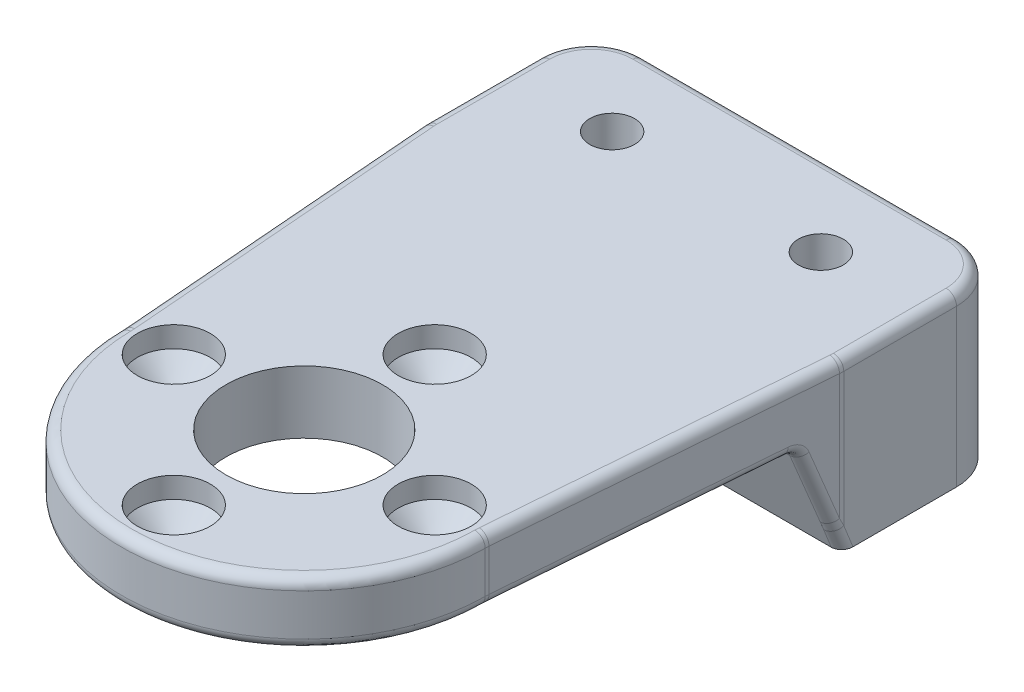
SolidWorks part; units mm, degrees
ref_plane "Front Plane" through (0, 0, 0) normal (0, 0, 1) x (1, 0, 0)
ref_plane "Top Plane" through (0, 0, 0) normal (0, 1, 0) x (1, 0, 0)
ref_plane "Right Plane" through (0, 0, 0) normal (1, 0, 0) x (0, 0, -1)
sketch "Sketch1" plane through (0, 0, 0) normal (0, 1, 0) x (1, 0, 0)
  circle A1 centre (-12.5, 0) radius 1.6
  circle A3 centre (0, 12.5) radius 1.6
  circle A5 centre (12.5, 0) radius 1.6
  circle A7 centre (0, -12.5) radius 1.6
  circle A10 centre (0, 0) radius 17.5
  circle A11 centre (0, 0) radius 7.5
  point P0 (0, 0)
  point P6 (0, 0)
  point P30 (0, 0)
  dimension "D4" = 3.2
  dimension "D1" = 15
  dimension "D2" = 35
  dimension "D5" = 12.5
  dimension "D7" = 4
extrude "Boss-Extrude1" add sketch "Sketch1" along normal blind 4
sketch "Sketch2" plane through (0, 4, 0) normal (0, 1, 0) x (1, 0, 0)
  circle A0 centre (0, -12.5) radius 1.6 construction
  circle A1 centre (0, 0) radius 17.5
  circle A2 centre (0, 0) radius 17.5
  circle A6 centre (0, -12.5) radius 3.5
  circle A7 centre (12.5, 0) radius 3.5
  circle A8 centre (0, 12.5) radius 3.5
  circle A9 centre (-12.5, 0) radius 3.5
  circle A10 centre (0, 0) radius 7.5 construction
  circle A11 centre (0, 0) radius 7.5
  dimension "D2" = 1.9
  dimension "D1" = 0
extrude "Boss-Extrude2" add sketch "Sketch2" along normal blind 2
sketch "Sketch3" plane through (0, 6, 0) normal (0, 1, 0) x (1, 0, 0)
  line L1 (-17.5, 0) -> (-20, 31.5)
  line L2 (17.5, 0) -> (20, 31.5)
  line L5 (-20, 31.5) -> (-20, 47.5)
  line L6 (-20, 47.5) -> (20, 47.5)
  line L7 (20, 31.5) -> (20, 47.5)
  circle A0 centre (0, 0) radius 17.5 construction
  circle A1 centre (0, 0) radius 17.5
  point P4 (0, 47.5)
  circle M6 centre (0, 0) radius 17.5
  dimension "D2" = 31.5
  dimension "D1" = 40
  dimension "D3" = 16
extrude "Boss-Extrude3" add sketch "Sketch3" against normal up to surface (6 mm away) contours L2 L7 L6 L5 L1 M6 region at (0, 6, -30.3876) up to face at (0, 0, 7.5)
sketch "Sketch4" plane through (0, 0, 0) normal (0, -1, 0) x (1, 0, 0)
  line L1 (-20, -47.5) -> (20, -47.5)
  line L2 (-20, -47.5) -> (-20, -31.5)
  line L3 (-20, -31.5) -> (20, -31.5)
  line L4 (20, -47.5) -> (20, -31.5)
extrude "Boss-Extrude4" add sketch "Sketch4" along normal blind 10
chamfer "Chamfer3" distance 4 distance2 10 1 edges at (0, 0, -31.5) first distance on face at (0, 0, 14.1)
fillet "Fillet2" radius 5 6 edges at (-17.5, 3, 0) (-20, -2, -31.5) (20, -2, -31.5) (17.5, 3, 0) (-20, -2, -47.5) (20, -2, -47.5)
fillet "Fillet3" radius 1 1 edges at (0, 0, -27.5)
fillet "Fillet4" radius 1 30 edges at (19.6733, -0.1719, -27.3836) (19.8434, -5.0675, -29.527) (19.999, -10, -31.599) (20, -10, -37.0991) (18.5355, -10, -46.0355) (0, -10, -47.5) (-18.5355, -10, -46.0355) (-20, -10, -37.0991) (-19.999, -10, -31.599) (-19.8434, -5.0675, -29.527) (-19.6733, -0.1719, -27.3836) (-18.5717, 0, -13.504) (-17.5039, 0, -0.0108) (0, 0, 17.5) (17.5039, 0, -0.0108) (17.5039, 6, -0.0108) (0, 6, 17.5) (-17.5039, 6, -0.0108) (-18.7495, 6, -15.7438) (-19.9961, 6, -31.5002) (-20, 6, -37.0991) (-18.5355, 6, -46.0355) (0, 6, -47.5) (18.5355, 6, -46.0355) (20, 6, -37.0991) (19.9961, 6, -31.5002) (18.5717, 0, -13.504) (18.7495, 6, -15.7438) (19.9912, -9.753, -31.4012) (-19.9912, -9.753, -31.4012)
sketch "Sketch5" plane through (0, -10, 0) normal (0, -1, 0) x (1, 0, 0)
  line L0 (0, -31.5) -> (0, -47.5) construction
  line L1 (19, -31.5) -> (-19, -31.5) construction
  line L2 (-15, -47.5) -> (15, -47.5) construction
  line L3 (-20, -32.577) -> (-20, -42.5) construction
  line L4 (-20, -37.5385) -> (20, -37.5385) construction
  line L5 (20, -42.5) -> (20, -32.577) construction
  circle A0 centre (-10, -39.5) radius 2.15
  circle A1 centre (10, -39.5) radius 2.15
  point P10 (0, -37.5385)
  point P11 (0, -39.5)
  dimension "D1" = 4.3
  dimension "D2" = 40
  dimension "D3" = 20
  dimension "D4" = 10
extrude "Cut-Extrude1" cut sketch "Sketch5" against normal through all
sketch "Sketch6" plane through (0, -10, 0) normal (0, -1, 0) x (1, 0, 0)
  line L0 (-13.6, -45.9217) -> (-13.6, -47.5)
  line L1 (-10, -35.3431) -> (-13.6, -37.4215)
  line L2 (-13.6, -37.4215) -> (-13.6, -45.9217)
  line L5 (-6.4, -45.7485) -> (-6.4, -37.4215)
  line L6 (-6.4, -37.4215) -> (-10, -35.3431)
  line L7 (10, -35.3431) -> (6.4, -37.4215)
  line L8 (6.4, -37.4215) -> (6.4, -45.5562)
  line L11 (13.6, -46.0762) -> (13.6, -37.4215)
  line L12 (13.6, -37.4215) -> (10, -35.3431)
  line L13 (-15, -47.5) -> (15, -47.5) construction
  line L14 (-13.6, -47.5) -> (-6.4, -47.5)
  line L15 (-6.4, -47.5) -> (-6.4, -45.7485)
  line L16 (6.4, -45.5562) -> (6.4, -47.5)
  line L17 (6.4, -47.5) -> (13.6, -47.5)
  line L18 (13.6, -47.5) -> (13.6, -46.0762)
  line L19 (-13.8839, -41.4146) -> (-12.0089, -42.4971) [skipped]
  line L20 (-9.1093, -43.1427) -> (-7.2343, -42.0602) [skipped]
  line L21 (9.1093, -43.1427) -> (10.9843, -44.2252) [skipped]
  line L22 (12.7093, -42.0927) -> (14.5843, -41.0102) [skipped]
  circle A0 centre (-10, -39.5) radius 3.6 construction
  circle A1 centre (10, -39.5) radius 3.6 construction
  dimension "D1" = 7.2
  dimension "D2" = 7.2
extrude "Cut-Extrude2" cut sketch "Sketch6" against normal blind 4 from offset 5.5 offset against normal yes
chamfer "Chamfer4" distance 1.9 angle 45 4 edges at (0, 4, 14.1) (12.5, 4, 1.6) (-12.5, 4, 1.6) (0, 4, -10.9)
equation "\"D4@Sketch5\"=\"D3@Sketch5\"/2"
